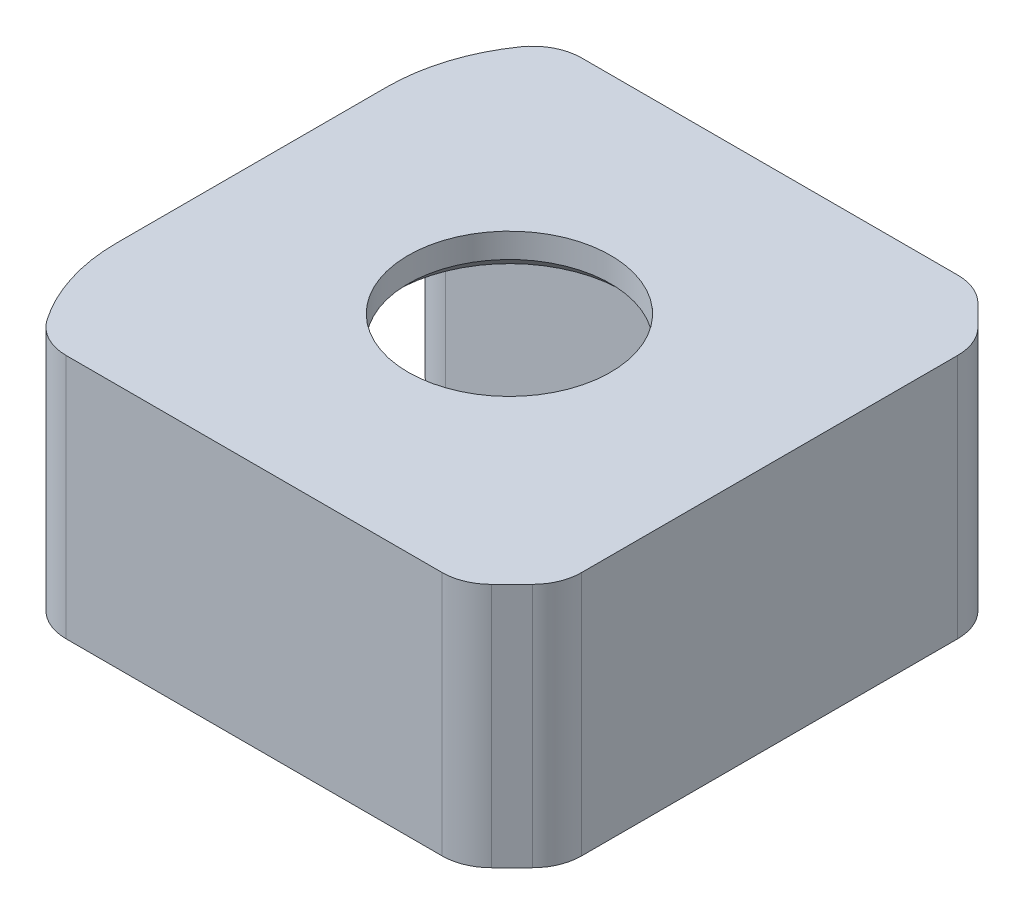
SolidWorks part; units mm, degrees
material "ABS"
ref_plane "Płaszczyzna przednia" through (0, 0, 0) normal (0, 0, 1) x (1, 0, 0)
ref_plane "Płaszczyzna górna" through (0, 0, 0) normal (0, 1, 0) x (1, 0, 0)
ref_plane "Płaszczyzna prawa" through (0, 0, 0) normal (1, 0, 0) x (0, 0, -1)
sketch "Szkic1" plane through (0, 0, 0) normal (0, 1, 0) x (1, 0, 0)
  line L0 (-50.0173, 36.2315) -> (-65.0121, 36.2315)
  line L1 (-30.6265, 36.7315) -> (-50.0173, 36.7315) construction
  line L2 (-30.6265, 36.7315) -> (-26.3173, 32.4223) construction
  line L3 (-30.6265, -6.2685) -> (-26.3173, -1.9594) construction
  line L4 (-69.0173, 26.2259) -> (-69.0173, 4.237)
  line L5 (-69.5173, 26.2259) -> (-69.5173, 4.237) construction
  line L6 (-50.0173, -5.7685) -> (-65.0121, -5.7685)
  line L7 (-50.0173, -5.7685) -> (-30.8336, -5.7685)
  line L8 (-30.8336, -5.7685) -> (-26.8173, -1.7523)
  line L9 (-50.0173, -6.2685) -> (-30.6265, -6.2685) construction
  line L10 (-26.8173, -1.7523) -> (-26.8173, 32.2152)
  line L11 (-26.3173, -1.9594) -> (-26.3173, 32.4223) construction
  line L12 (-50.0173, 36.7315) -> (-65.224, 36.7315) construction
  line L13 (-50.0173, -6.2685) -> (-65.224, -6.2685) construction
  line L14 (-30.8336, 36.2315) -> (-26.8173, 32.2152)
  line L15 (-30.8336, 36.2315) -> (-50.0173, 36.2315)
  circle A0 centre (-63.5173, -0.2685) radius 1.65
  circle A1 centre (-32.5173, -0.2685) radius 1.65
  circle A2 centre (-32.5173, 30.7315) radius 1.65
  circle A3 centre (-63.5173, 30.7315) radius 1.65
  circle A4 centre (-48.0173, 15.2315) radius 9.3 construction
  arc A5 (-65.0121, 36.2315) -> (-69.0173, 26.2259) centre (-54.5173, 26.2259) ccw
  arc A6 (-69.0173, 4.237) -> (-65.0121, -5.7685) centre (-54.5173, 4.237) ccw
  circle A7 centre (-48.0173, 15.2315) radius 9
  circle A8 centre (-48.0173, 15.2315) radius 11
  circle A9 centre (-48.0173, 15.2315) radius 11.95
  arc A11 (-65.224, 36.7315) -> (-69.5173, 26.2259) centre (-54.5173, 26.2259) ccw construction
  arc A12 (-69.5173, 4.237) -> (-65.224, -6.2685) centre (-54.5173, 4.237) ccw construction
  circle A18 centre (-48.0173, 15.2315) radius 5.4773
  circle A19 centre (-48.0173, 15.2315) radius 11.3 construction
  circle A20 centre (-48.0173, 15.2315) radius 12.25 construction
  circle A21 centre (-48.0173, 15.2315) radius 2.5 construction
  dimension "D1" = 0.5
  dimension "D2" = 0.3
  dimension "D3" = 0.3
  dimension "D4" = 0.3
extrude "Dodanie-wyciągnięcie1" add sketch "Szkic1" along normal blind 8 contours A7 A18 region at (-56.7628, 0, -15.2315)
extrude "Dodanie-wyciągnięcie2" add sketch "Szkic1<3>" along normal blind 7 contours A8 A7 region at (-58.7062, 0, -15.2315)
sketch "Szkic1<3>" plane through (0, 0, 0) normal (0, 1, 0) x (1, 0, 0) same geometry as "Szkic1"
extrude "Dodanie-wyciągnięcie3" add sketch "Szkic1<4>" along normal blind 3 contours A9 A8 region at (-59.6293, 0, -15.2315)
sketch "Szkic1<4>" plane through (0, 0, 0) normal (0, 1, 0) x (1, 0, 0) same geometry as "Szkic1"
extrude "Dodanie-wyciągnięcie4" add sketch "Szkic1<5>" against normal blind 3 contours L4 A6 L6 L7 L8 L10 L14 L15 L0 A5 A9 A0 A1 A2 A3 | A9 A8 | A8 A7 | A7 A18 region at (-40.4254, 0, -35.6361) region at (-56.7628, 0, -15.2315) region at (-58.7062, 0, -15.2315) region at (-59.6293, 0, -15.2315)
sketch "Szkic1<5>" plane through (0, 0, 0) normal (0, 1, 0) x (1, 0, 0) same geometry as "Szkic1"
sketch "Szkic2" plane through (0, -3, 0) normal (0, -1, 0) x (1, 0, 0)
  circle A0 centre (-48.0173, -15.2315) radius 8.25
  dimension "D1" = 16.5
extrude "Wytnij-wyciągnięcie1" cut sketch "Szkic2" against normal blind 5
chamfer "Sfazowanie1" distance 1.2 angle 45 1 edges at (-48.0173, 3, -3.2815)
sketch "Szkic3" plane through (0, -3, 0) normal (0, -1, 0) x (1, 0, 0)
  line L0 (-69.0173, -26.2259) -> (-36.8173, -26.2259)
  line L1 (-36.8173, -26.2259) -> (-36.8173, -4.237)
  line L2 (-36.8173, -4.237) -> (-69.0173, -4.237)
  line L4 (-26.8173, 1.7523) -> (-26.8173, -32.2152) construction
  line L11 (-69.0173, -4.237) -> (-69.0173, -26.2259)
  line L12 (-65.0121, -36.2315) -> (-30.8336, -36.2315)
  line L13 (-30.8336, -36.2315) -> (-26.8173, -32.2152)
  line L14 (-26.8173, -32.2152) -> (-26.8173, 1.7523)
  line L15 (-26.8173, 1.7523) -> (-30.8336, 5.7685)
  line L16 (-30.8336, 5.7685) -> (-65.0121, 5.7685)
  line L18 (-65.0121, -36.2315) -> (-30.8336, -36.2315)
  line L19 (-30.8336, -36.2315) -> (-26.8173, -32.2152)
  line L20 (-26.8173, -32.2152) -> (-26.8173, 1.7523)
  line L21 (-26.8173, 1.7523) -> (-30.8336, 5.7685)
  line L22 (-30.8336, 5.7685) -> (-65.0121, 5.7685)
  circle A0 centre (-63.5173, 0.2685) radius 1.65 construction
  circle A1 centre (-32.5173, 0.2685) radius 1.65 construction
  arc A2 (-69.0173, -26.2259) -> (-65.0121, -36.2315) centre (-54.5173, -26.2259) ccw
  arc A3 (-65.0121, 5.7685) -> (-69.0173, -4.237) centre (-54.5173, -4.237) ccw
  arc A4 (-69.0173, -26.2259) -> (-65.0121, -36.2315) centre (-54.5173, -26.2259) ccw
  arc A5 (-65.0121, 5.7685) -> (-69.0173, -4.237) centre (-54.5173, -4.237) ccw
  circle A6 centre (-32.5173, -30.7315) radius 1.65 construction
  circle A7 centre (-63.5173, -30.7315) radius 1.65 construction
  circle A8 centre (-63.5173, 0.2685) radius 1.65
  circle A9 centre (-32.5173, 0.2685) radius 1.65
  circle A10 centre (-32.5173, -30.7315) radius 1.65
  circle A11 centre (-63.5173, -30.7315) radius 1.65
  dimension "D1" = 10
  dimension "D2" = 0
extrude "Dodanie-wyciągnięcie5" add sketch "Szkic3" along normal blind 17
fillet "Zaokrąglenie1" radius 10 2 edges at (-36.8173, -11.5, -26.2259) (-36.8173, -11.5, -4.237)
fillet "Zaokrąglenie2" radius 4 8 edges at (-30.8336, -10, 5.7685) (-26.8173, -10, 1.7523) (-26.8173, -10, -32.2152) (-30.8336, -10, -36.2315) (-65.0121, -10, -36.2315) (-65.0121, -10, 5.7685) (-69.0173, -11.5, -26.2259) (-69.0173, -11.5, -4.237)
chamfer "Sfazowanie2" distance 2 angle 45 1 edges at (-48.0173, 7, -4.2315)
sketch "Szkic5" plane through (0, 0, 0) normal (0, 1, 0) x (1, 0, 0)
  line L6 (-63.1303, -5.7685) -> (-32.4904, -5.7685)
  line L7 (-29.662, -4.597) -> (-27.9889, -2.9239)
  line L8 (-26.8173, -0.0955) -> (-26.8173, 30.5584)
  line L9 (-27.9889, 33.3868) -> (-29.662, 35.0599)
  line L10 (-32.4904, 36.2315) -> (-63.1303, 36.2315)
  line L11 (-69.0173, 26.2259) -> (-69.0173, 4.237)
  line L12 (-63.1303, -5.7685) -> (-32.4904, -5.7685)
  line L13 (-29.662, -4.597) -> (-27.9889, -2.9239)
  line L14 (-26.8173, -0.0955) -> (-26.8173, 30.5584)
  line L15 (-27.9889, 33.3868) -> (-29.662, 35.0599)
  line L16 (-32.4904, 36.2315) -> (-63.1303, 36.2315)
  line L17 (-69.0173, 26.2259) -> (-69.0173, 4.237)
  arc A8 (-32.4904, -5.7685) -> (-29.662, -4.597) centre (-32.4904, -1.7685) ccw
  arc A9 (-27.9889, -2.9239) -> (-26.8173, -0.0955) centre (-30.8173, -0.0955) ccw
  arc A10 (-26.8173, 30.5584) -> (-27.9889, 33.3868) centre (-30.8173, 30.5584) ccw
  arc A11 (-29.662, 35.0599) -> (-32.4904, 36.2315) centre (-32.4904, 32.2315) ccw
  arc A12 (-63.1303, 36.2315) -> (-66.4115, 34.5193) centre (-63.1303, 32.2315) ccw
  arc A13 (-66.4115, 34.5193) -> (-69.0173, 26.2259) centre (-54.5173, 26.2259) ccw
  arc A14 (-69.0173, 4.237) -> (-66.4115, -4.0564) centre (-54.5173, 4.237) ccw
  arc A15 (-66.4115, -4.0564) -> (-63.1303, -5.7685) centre (-63.1303, -1.7685) ccw
  arc A16 (-32.4904, -5.7685) -> (-29.662, -4.597) centre (-32.4904, -1.7685) ccw
  arc A17 (-27.9889, -2.9239) -> (-26.8173, -0.0955) centre (-30.8173, -0.0955) ccw
  arc A18 (-26.8173, 30.5584) -> (-27.9889, 33.3868) centre (-30.8173, 30.5584) ccw
  arc A19 (-29.662, 35.0599) -> (-32.4904, 36.2315) centre (-32.4904, 32.2315) ccw
  arc A20 (-63.1303, 36.2315) -> (-66.4115, 34.5193) centre (-63.1303, 32.2315) ccw
  arc A21 (-66.4115, 34.5193) -> (-69.0173, 26.2259) centre (-54.5173, 26.2259) ccw
  arc A22 (-69.0173, 4.237) -> (-66.4115, -4.0564) centre (-54.5173, 4.237) ccw
  arc A23 (-66.4115, -4.0564) -> (-63.1303, -5.7685) centre (-63.1303, -1.7685) ccw
  dimension "D1" = 0
extrude "Wytnij-wyciągnięcie3" cut sketch "Szkic5" along normal through all
chamfer "Sfazowanie3" distance 1 angle 45 1 edges at (-48.0173, -3, -23.4815)
chamfer "Sfazowanie4" distance 1 angle 45 3 edges at (-68.7414, -3, -29.0414) (-68.7414, -3, -1.4215) (-69.0173, -3, -15.2315)
sketch "Szkic6" plane through (0, 0, 0) normal (0, 1, 0) x (1, 0, 0)
  circle A0 centre (-32.5173, -0.2685) radius 1.65 construction
  circle A1 centre (-32.5173, 30.7315) radius 1.65 construction
  circle A2 centre (-63.5173, 30.7315) radius 1.65 construction
  circle A3 centre (-63.5173, -0.2685) radius 1.65 construction
  circle A4 centre (-32.5173, -0.2685) radius 1.65
  circle A5 centre (-32.5173, 30.7315) radius 1.65
  circle A6 centre (-63.5173, 30.7315) radius 1.65
  circle A7 centre (-63.5173, -0.2685) radius 1.65
extrude "Dodanie-wyciągnięcie6" add sketch "Szkic6" against normal blind 0.2
